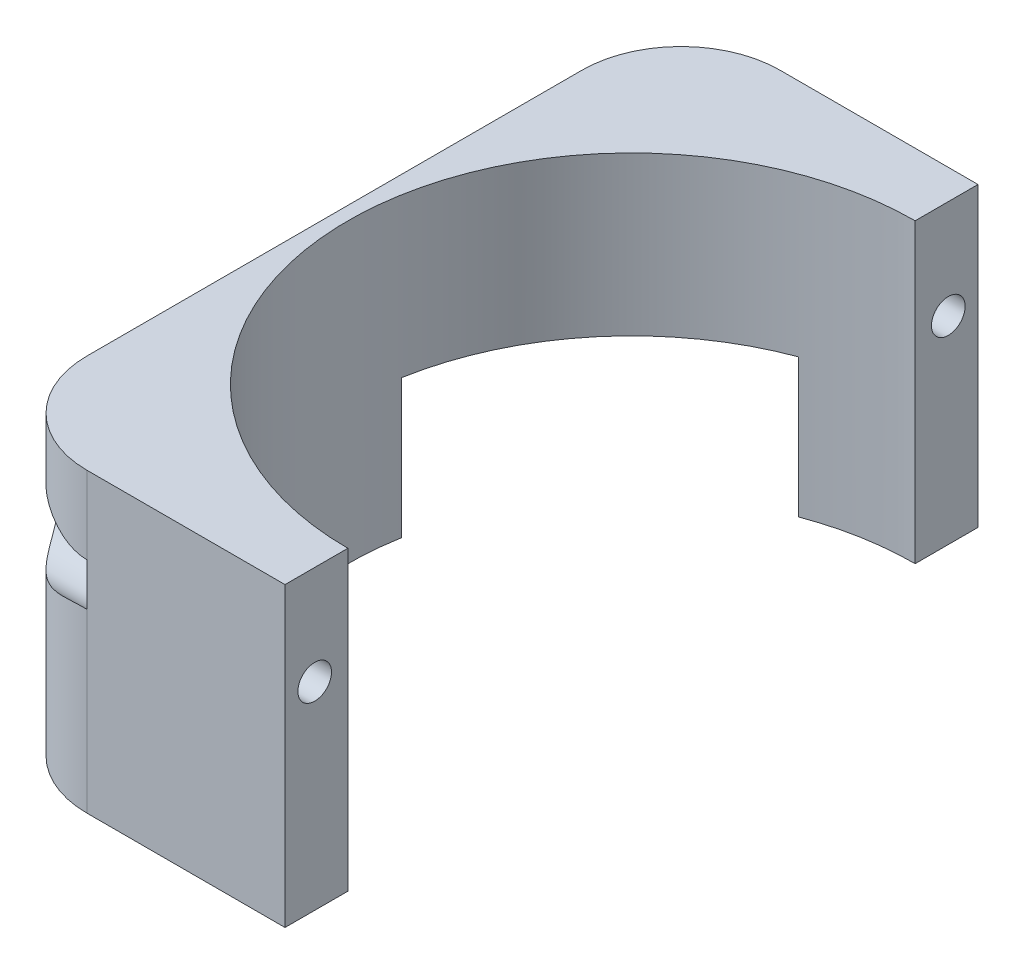
SolidWorks part; units mm, degrees
ref_plane "前视基准面" through (0, 0, 0) normal (0, 0, 1) x (1, 0, 0)
ref_plane "上视基准面" through (0, 0, 0) normal (0, 1, 0) x (1, 0, 0)
ref_plane "右视基准面" through (0, 0, 0) normal (1, 0, 0) x (0, 0, -1)
sketch "草图1" plane through (0, 0, 0) normal (0, 1, 0) x (1, 0, 0)
  line L1 (-30, 35) -> (30, 35)
  line L2 (-30, 35) -> (-30, -35)
  line L3 (-30, -35) -> (30, -35)
  line L4 (30, 35) -> (30, -35)
  line L5 (-30, 35) -> (30, -35) construction
  line L6 (-30, -35) -> (30, 35) construction
  circle A0 centre (0, 0) radius 28.65
  point P0 (0, 0)
  dimension "D3" = 57.3
  dimension "D1" = 70
  dimension "D2" = 60
extrude "凸台-拉伸1" add sketch "草图1" along normal blind 30
sketch "草图2" plane through (0, 30, 0) normal (0, 1, 0) x (1, 0, 0)
  line L1 (0, 46.2262) -> (76.0724, 46.2262)
  line L2 (0, 46.2262) -> (0, -42.4462)
  line L3 (0, -42.4462) -> (76.0724, -42.4462)
  line L4 (76.0724, 46.2262) -> (76.0724, -42.4462)
extrude "切除-拉伸1" cut sketch "草图2" against normal blind 30
sketch "草图3" plane through (0, 0, 0) normal (1, 0, 0) x (0, 0, -1)
  line L0 (-28.65, 0) -> (28.65, 0) construction
  circle A0 centre (32, 20) radius 1.7
  circle A1 centre (-32, 20) radius 1.7
  dimension "D1" = 32
  dimension "D2" = 3.4
  dimension "D3" = 20
  dimension "D4" = 3.4
  dimension "D5" = 32
  dimension "D6" = 20
extrude "切除-拉伸2" cut sketch "草图3" against normal blind 40
sketch "草图4" plane through (0, 0, -35) normal (0, 0, -1) x (-1, 0, 0)
  line L1 (30, 0) -> (10, 0)
  line L2 (30, 0) -> (30, 14)
  line L3 (30, 14) -> (10, 14)
  line L4 (10, 0) -> (10, 14)
  dimension "D1" = 20
  dimension "D2" = 14
extrude "切除-拉伸3" cut sketch "草图4" against normal blind 30
sketch "草图5" plane through (-30, 0, 0) normal (-1, 0, 0) x (0, 0, 1)
  circle A0 centre (-32, 20) radius 3.7
  circle A1 centre (32, 20) radius 3.7
  dimension "D1" = 7.4
  dimension "D2" = 7.4
extrude "切除-拉伸4" cut sketch "草图5" against normal blind 10
fillet "圆角1" radius 10 2 edges at (-30, 26.0828, 35) (-30, 26.0828, -35)
